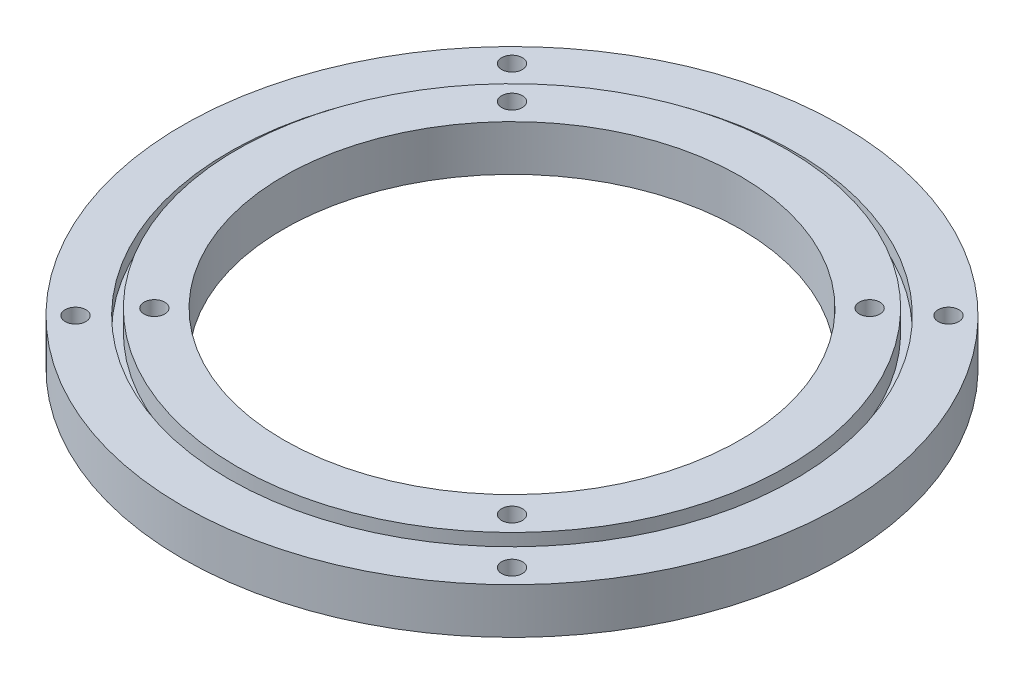
SolidWorks part; units mm, degrees
ref_plane "Front Plane" through (0, 0, 0) normal (0, 0, 1) x (1, 0, 0)
ref_plane "Top Plane" through (0, 0, 0) normal (0, 1, 0) x (1, 0, 0)
ref_plane "Right Plane" through (0, 0, 0) normal (1, 0, 0) x (0, 0, -1)
sketch "Sketch1" plane through (0, 0, 0) normal (0, 1, 0) x (1, 0, 0)
  line L0 (0, 0) -> (54.8008, 54.8008) construction
  line L1 (-70, 0) -> (-85.5, 0) construction
  line L2 (-85.5, 0) -> (-101, 0) construction
  circle A0 centre (0, 0) radius 101
  circle A1 centre (0, 0) radius 70
  circle A2 centre (54.8008, 54.8008) radius 3.175
  circle A3 centre (0, 0) radius 85.5 construction
  circle A4 centre (0, 0) radius 86.77
  circle A5 centre (0, 0) radius 84.23
  circle A6 centre (66.8888, 66.8888) radius 3.175
  circle A7 centre (66.8888, -66.8888) radius 3.175
  circle A8 centre (54.8008, -54.8008) radius 3.175
  circle A9 centre (-66.8888, -66.8888) radius 3.175
  circle A10 centre (-54.8008, -54.8008) radius 3.175
  circle A11 centre (-66.8888, 66.8888) radius 3.175
  circle A12 centre (-54.8008, 54.8008) radius 3.175
  point P14 (0, 0)
  point P15 (71.4178, 71.4178)
  point P18 (69.1338, 69.1338)
  point P19 (66.8911, 66.8911)
  point P33 (0, 0)
  dimension "D1" = 202
  dimension "D2" = 140
  dimension "D4" = 6.35
  dimension "D7" = 4
  dimension "D10" = 6.35
  dimension "D3" = 77.5
  dimension "D8" = 45
  dimension "D9" = 3.23
  dimension "D5" = 1.27
  dimension "D6" = 1.27
extrude "Boss-Extrude1" add sketch "Sketch1" along normal mid plane 12 contours A0 A9 A6 A4 A7 A11 | A5 A12 A10 A8 A2 A1 region at (-98.1433, 0, 0) region at (-81.8476, 0, 0)
extrude "Boss-Extrude2" add sketch "Sketch1<3>" along normal mid plane 3.175 contours A4 A5 region at (-84.3158, 0, 0)
sketch "Sketch1<3>" plane through (0, 0, 0) normal (0, 1, 0) x (1, 0, 0) same geometry as "Sketch1"
extrude "Boss-Extrude3" add sketch "Sketch1<4>" along normal blind 2 from surface contours A5 A12 A10 A8 A2 A1 region at (-81.8476, 0, 0) starting at face at (-54.8008, 6, -51.6258)
sketch "Sketch1<4>" plane through (0, 0, 0) normal (0, 1, 0) x (1, 0, 0) same geometry as "Sketch1"
extrude "Boss-Extrude4" add sketch "Sketch1<5>" against normal blind 2 from surface contours A0 A9 A6 A4 A7 A11 region at (-98.1433, 0, 0) starting at face at (-66.8888, -6, 70.0638)
sketch "Sketch1<5>" plane through (0, 0, 0) normal (0, 1, 0) x (1, 0, 0) same geometry as "Sketch1"
